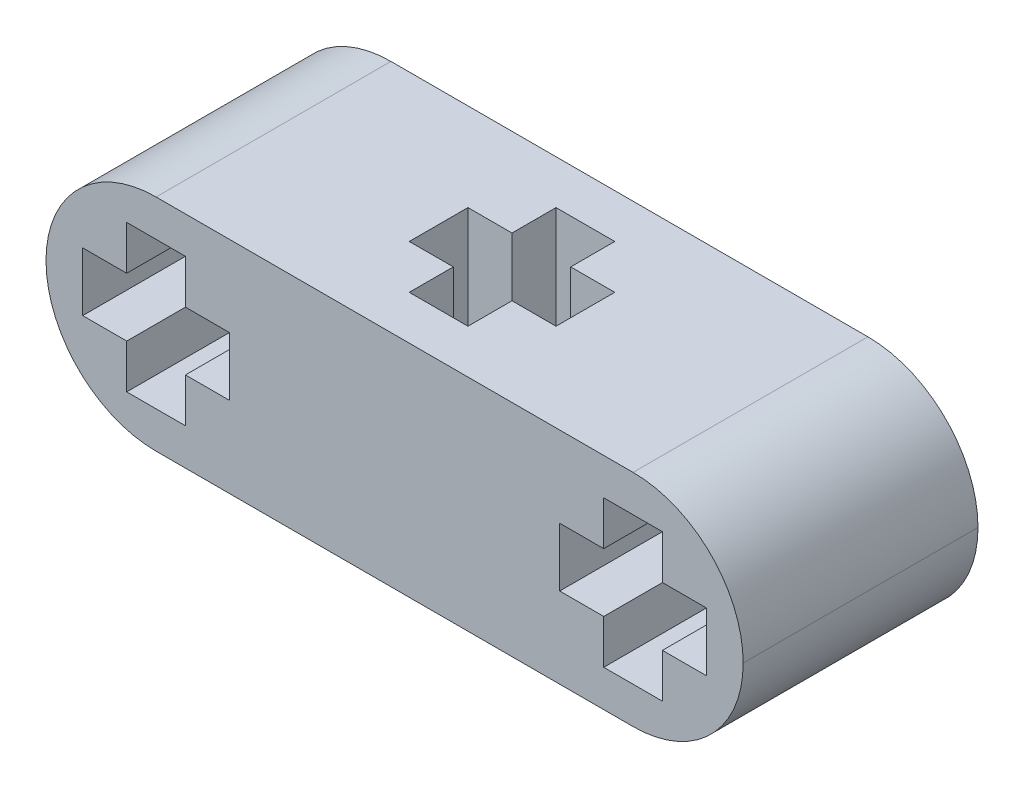
SolidWorks part; units mm, degrees
material "PVC 0.007 Plasticized"
ref_plane "Front Plane" through (0, 0, 0) normal (0, 0, 1) x (1, 0, 0)
ref_plane "Top Plane" through (0, 0, 0) normal (0, 1, 0) x (1, 0, 0)
ref_plane "Right Plane" through (0, 0, 0) normal (1, 0, 0) x (0, 0, -1)
sketch "Sketch1" plane through (0, 0, 0) normal (0, 0, 1) x (1, 0, 0)
  line L1 (0, 0) -> (23.75, 0)
  line L2 (0, 0) -> (0, 7.5)
  line L3 (0, 7.5) -> (23.75, 7.5)
  line L4 (23.75, 0) -> (23.75, 7.5)
  dimension "D1" = 23.75
  dimension "D2" = 7.5
extrude "Boss-Extrude1" add sketch "Sketch1" along normal blind 8
fillet "Fillet1" radius 3.75 2 edges at (23.75, 0, 4) (23.75, 7.5, 4)
fillet "Fillet2" radius 3.75 2 edges at (0, 0, 4) (0, 7.5, 4)
sketch "Sketch6" plane through (0, 0, 0) normal (0, 0, -1) x (-1, 0, 0)
  line L0 (-11.875, 7.5) -> (-11.875, 0)
  line L1 (-20, 7.5) -> (-3.75, 7.5) construction
  line L2 (-3.75, 0) -> (-20, 0) construction
ref_plane "Plane8" through (0, 0, 4) normal (0, 0, -1) x (-1, 0, 0)
ref_plane "Plane11" through (20, 7.5, 8) normal (0, 0, -1) x (-1, 0, 0)
sketch "Sketch17" plane through (0, 0, 8) normal (0, 0, 1) x (1, 0, 0)
  line L0 (20, 7.5) -> (20, 0)
  line L1 (20, 3.75) -> (22.5, 3.75)
  line L2 (22.5, 3.75) -> (22.5, 4.75)
  line L3 (22.5, 4.75) -> (21, 4.75)
  line L4 (21, 4.75) -> (21, 6.25)
  line L5 (21, 6.25) -> (19, 6.25)
  line L6 (19, 6.25) -> (19, 4.75)
  line L7 (19, 4.75) -> (17.5, 4.75)
  line L8 (17.5, 4.75) -> (17.5, 2.75)
  line L9 (17.5, 2.75) -> (19, 2.75)
  line L10 (19, 2.75) -> (19, 1.25)
  line L11 (19, 1.25) -> (21, 1.25)
  line L12 (21, 1.25) -> (21, 2.75)
  line L13 (21, 2.75) -> (22.5, 2.75)
  line L14 (22.5, 2.75) -> (22.5, 3.75)
extrude "Cut-Extrude13" cut sketch "Sketch17" against normal through all contours L4 L5 L0 L1 L2 L3 | L10 L11 L0 L5 L6 L7 L8 L9 | L13 L14 L1 L0 L11 L12 region at (20.9688, 4.7187, 8) region at (19.0313, 3.75, 8) region at (20.9688, 2.7813, 8)
ref_plane "Plane12" through (11.875, 0, 0) normal (1, 0, 0) x (0, 0, -1)
mirror "Mirror4" about plane through (11.875, 0, 0) normal (1, 0, 0) of "Cut-Extrude13"
sketch "Sketch18" plane through (0, 7.5, 0) normal (0, 1, 0) x (1, 0, 0)
  line L0 (20, 0) -> (3.75, -8) construction
  point P2 (11.875, -4)
  line B0 (11.875, -0.25) -> (11.875, -7.75)
  line B1 (11.875, -4) -> (14.375, -4)
  line B2 (14.375, -4) -> (14.375, -3)
  line B3 (14.375, -3) -> (12.875, -3)
  line B4 (12.875, -3) -> (12.875, -1.5)
  line B5 (12.875, -1.5) -> (10.875, -1.5)
  line B6 (10.875, -1.5) -> (10.875, -3)
  line B7 (10.875, -3) -> (9.375, -3)
  line B8 (9.375, -3) -> (9.375, -5)
  line B9 (9.375, -5) -> (10.875, -5)
  line B10 (10.875, -5) -> (10.875, -6.5)
  line B11 (10.875, -6.5) -> (12.875, -6.5)
  line B12 (12.875, -6.5) -> (12.875, -5)
  line B13 (12.875, -5) -> (14.375, -5)
  line B14 (14.375, -5) -> (14.375, -4)
sketch_block_instance "Block1-1"
sketch_block "Block1"
extrude "Cut-Extrude14" cut sketch "Sketch18" against normal blind 10 contours B13 B14 B1 B0 B11 B12 | L0 B3 B4 B5 B0 | B3 L0 B1 B2 | L0 B0 B5 B6 B7 B8 B9 | B0 L0 B9 B10 B11 region at (13.517, 7.5, 3.614) region at (12.4465, 7.5, 2.6874) region at (11.3035, 7.5, 5.3126) region at (10.724, 7.5, 3.3979) region at (12.8437, 7.5, 4.9687)
